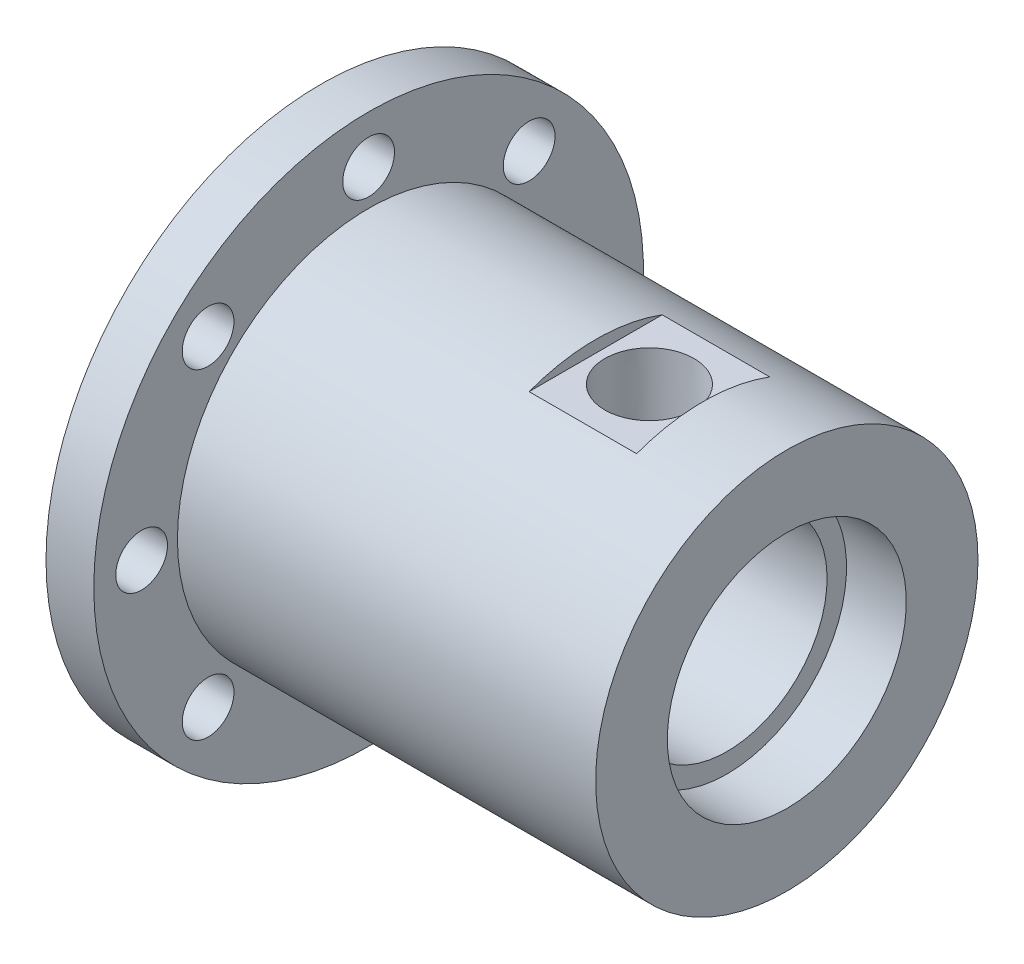
SolidWorks part; units mm, degrees
ref_plane "Front Plane" through (0, 0, 0) normal (0, 0, 1) x (1, 0, 0)
ref_plane "Top Plane" through (0, 0, 0) normal (0, 1, 0) x (1, 0, 0)
ref_plane "Right Plane" through (0, 0, 0) normal (1, 0, 0) x (0, 0, -1)
sketch "Sketch1" plane through (0, 0, 0) normal (0, 0, 1) x (1, 0, 0)
  line L0 (-30.6578, 10.6299) -> (-30.6578, 11.9507)
  line L1 (-49.53, 0) -> (-49.53, 12.7)
  line L2 (-49.53, 12.7) -> (-34.29, 12.7)
  line L3 (-34.29, 12.7) -> (-34.29, 10.6299)
  line L4 (-34.29, 10.6299) -> (-33.02, 10.6299)
  line L5 (-28.8798, 10.6299) -> (-28.8798, 11.9507)
  line L6 (-28.8798, 11.9507) -> (-26.5176, 11.9507)
  line L7 (-26.5176, 11.9507) -> (-26.5176, 10.6299)
  line L11 (-6.35, 10.6299) -> (-6.35, 12.7)
  line L12 (-6.35, 12.7) -> (0, 12.7)
  line L16 (0, 0) -> (-49.53, 0)
  line L17 (-30.6578, 11.9507) -> (-33.02, 11.9507)
  line L18 (-33.02, 11.9507) -> (-33.02, 10.6299)
  line L19 (-30.6578, 10.6299) -> (-28.8798, 10.6299)
  line L20 (0, 0) -> (0, 12.7)
  line L21 (-26.5176, 10.6299) -> (-6.35, 10.6299)
  dimension "D1" = 6.35
  dimension "D2" = 2.3622
  dimension "D3" = 1.3208
  dimension "D9" = 1.27
  dimension "D10" = 12.7
  dimension "D11" = 15.24
  dimension "D7" = 12.7
  dimension "D4" = 11.9507
  dimension "D12" = 1.778
  dimension "D5" = 49.53
sketch "Sketch2" plane through (0, 0, 0) normal (1, 0, 0) x (0, 0, -1)
  circle A0 centre (0, 0) radius 20.32
  dimension "D1" = 40.64
extrude "Boss-Extrude1" add sketch "Sketch2" against normal blind 49.53
revolve "Cut-Revolve1" cut sketch "Sketch1" angle 360 about L16
sketch "Sketch3" plane through (-49.53, 0, 0) normal (-1, 0, 0) x (0, 0, 1)
  circle A0 centre (0, 0) radius 19.05
  circle A1 centre (0, 0) radius 29.21
  dimension "D1" = 58.42
extrude "Boss-Extrude2" add sketch "Sketch3" against normal blind 5.08
sketch "Sketch4" plane through (-44.45, 0, 0) normal (1, 0, 0) x (0, 0, -1)
  circle A2 centre (0, 0) radius 24.13
  circle A3 centre (0, 0) radius 24.13 construction
  point P0 (0, 24.13)
  point P12 (0, 0)
  point P15 (0, 0)
  point P78 (17.0625, 17.0625)
  point P79 (24.13, 0)
  point P80 (17.0625, -17.0625)
  point P81 (0, -24.13)
  point P82 (-17.0625, -17.0625)
  point P83 (-24.13, 0)
  point P84 (-17.0625, 17.0625)
  dimension "D1" = 5.08
  dimension "D2" = 8
hole_wizard "M5 Clearance Hole1" positions "Sketch4" profile "Sketch5" hole size "M5" standard "ISO" end condition up to next
sketch "Sketch5" plane through (-44.45, 24.13, 0) normal (0, 1, 0) x (0, 0, -1)
  line L0 (0, 0) -> (0, 5.08)
  line L1 (0, 5.08) -> (2.75, 5.08)
  line L2 (2.75, 5.08) -> (2.75, 0)
  line L5 (2.75, 0) -> (0, 0)
  line L11 (0, -6.35) -> (0, 107.95) construction
  dimension "Thru Hole Dia." = 5.5
  dimension "Thru Hole Depth" = 5.08
ref_plane "Plane1" through (0, 20.32, 0) normal (0, 1, 0) x (1, 0, 0)
sketch "Sketch6" plane through (0, 20.32, 0) normal (0, 1, 0) x (1, 0, 0)
  line L0 (0, 0) -> (-8.89, 0) construction
  line L1 (-20.32, 12.7) -> (-8.89, 12.7)
  line L2 (-20.32, 12.7) -> (-20.32, -12.7)
  line L3 (-20.32, -12.7) -> (-8.89, -12.7)
  line L4 (-8.89, 12.7) -> (-8.89, -12.7)
  line L5 (0, -20.32) -> (0, 20.32) construction
  dimension "D1" = 8.89
  dimension "D2" = 11.43
  dimension "D3" = 25.4
extrude "Cut-Extrude1" cut sketch "Sketch6" against normal blind 1.27
sketch "Sketch7" plane through (0, 19.05, 0) normal (0, 1, 0) x (1, 0, 0)
  line L0 (-20.32, 7.0711) -> (-8.89, -7.0711) construction
  line L1 (-8.89, 7.0711) -> (-20.32, -7.0711) construction
  point P8 (-14.605, 0)
hole_wizard "1/8 NPT Tapped Hole1" positions "Sketch7" profile "Sketch8" size "1/8" standard "ANSI Inch" end condition up to next
sketch "Sketch8" plane through (-14.605, 19.05, 0) normal (1, 0, 0) x (0, 0, 1)
  line L0 (0, 0) -> (0, 8.4201)
  line L1 (0, 8.4201) -> (4.2164, 8.4201)
  line L2 (-4.5374, 6.858) -> (-4.7427, 0) construction
  line L3 (4.2164, 8.4201) -> (4.2164, 6.858)
  line L4 (4.2164, 6.858) -> (4.5374, 6.858)
  line L5 (4.5374, 6.858) -> (4.7427, 0)
  line L7 (4.7427, 0) -> (0, 0)
  line L8 (0, -6.35) -> (0, 107.95) construction
  line L11 (-4.2164, 6.858) -> (-4.5374, 6.858) construction
  dimension "Thru Tap Drill Dia." = 8.4328
  dimension "Thru Tap Drill Depth" = 8.4201
  dimension "Thread Dia." = 9.4855
  dimension "Thread Angle" = 3.43
  dimension "Thread Depth" = 6.858
cosmetic thread "Hole Thread1" parameters "D1"=6.858, "D2"=10.2827
equation "\"lip_seal_width\"= 0.25in"
equation "\"D1@Sketch1\"=\"lip_seal_width\""
equation "\"Cavity_Depth\" = 0.031in"
equation "\"Cavity_Width\" = 0.031in"
equation "\"Tooth_Width\" = .01in"
equation "\"Shaft_Seal_OD\"= 17mm'diameter at seal area"
equation "\"Shaft_clearance\"= .002in"
equation "\"O-Ring_ID\"= .801in"
equation "\"O-Ring_CS\"= .070in"
equation "\"Shaft_OD\"= .5in"
equation "\"post_laby_len\"= 1.25in"
equation "\"lip_seal_OD\"= 1in"
equation "\"D7@Sketch1\"=\"lip_seal_OD\"/2"
equation "\"Casing_OD\"= 1.6in"
equation "\"D1@Sketch2\"=\"Casing_OD\""
equation "\"D4@Sketch1\"=\"O-Ring_ID\"/2 + \"O-Ring_CS\""
equation "\"Flange_OD\"=2.3in"
equation "\"D1@Sketch3\"=\"Flange_OD\""
equation "\"D1@Sketch6\"=\"lip_seal_width\"+.1"
equation "\"total_len\"= 1.95"
equation "\"D5@Sketch1\"=\"total_len\""
equation "\"D1@Boss-Extrude1\"=\"total_len\""
